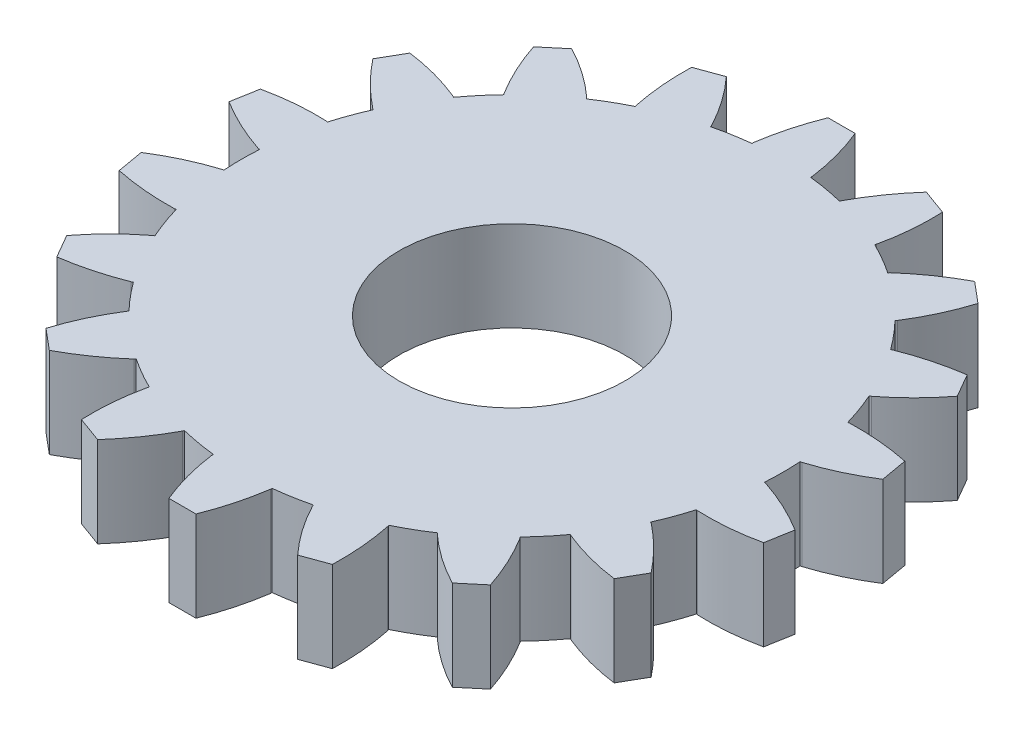
SolidWorks part; units mm, degrees
ref_plane "Front Plane" through (0, 0, 0) normal (0, 0, 1) x (1, 0, 0)
ref_plane "Top Plane" through (0, 0, 0) normal (0, 1, 0) x (1, 0, 0)
ref_plane "Right Plane" through (0, 0, 0) normal (1, 0, 0) x (0, 0, -1)
sketch "Sketch1" plane through (0, 0, 0) normal (0, 1, 0) x (1, 0, 0)
  circle A0 centre (0, 0) radius 6
  dimension "D1" = 12
extrude "Boss-Extrude1" add sketch "Sketch1" along normal blind 2
sketch "Sketch2" plane through (0, 2, 0) normal (0, 1, 0) x (1, 0, 0)
  circle A0 centre (0, 0) radius 1.25
  dimension "D1" = 2.5
extrude "Cut-Extrude1" cut sketch "Sketch2" against normal blind 4 and the other way blind 3
sketch "Sketch3" plane through (0, 2, 0) normal (0, 1, 0) x (1, 0, 0)
  circle A0 centre (0, 0) radius 2
  circle A1 centre (0, 0) radius 0.75
extrude "Boss-Extrude2" add sketch "Sketch3" along normal blind 0.2 and the other way blind 2.2
sketch "Sketch4" plane through (0, 2, 0) normal (0, 1, 0) x (1, 0, 0)
  line L3 (-0.3, 7.3) -> (0.3, 7.3)
  line L4 (-0.65, 6) -> (-0.65, 5.9647)
  line L5 (0.65, 6) -> (0.65, 5.9647)
  arc A1 (-0.3, 7.3) -> (-0.65, 6) centre (5.0734, 5.1562) ccw
  arc A2 (0.3, 7.3) -> (0.65, 6) centre (-4.488, 5.3138) cw
  arc A3 (0.65, 5.9647) -> (-0.65, 5.9647) centre (0, 0) ccw
  point P8 (-0.325, 6)
  point P11 (0, 7.3)
  dimension "D1" = 0.6
extrude "Boss-Extrude3" add sketch "Sketch4" against normal up to surface (2 mm away) up to face at (0, 0, 2)
ref_axis "Axis1" through (0, 2.32, 0) along (0, -1, 0)
pattern_circular "CirPattern1" count 18 over 360 about axis through (0, 2.32, 0) along (0, -1, 0) of "Boss-Extrude3"
sketch "Sketch5" plane through (0, 2, 0) normal (0, 1, 0) x (1, 0, 0)
  circle A0 centre (0, 0) radius 2.5
extrude "Cut-Extrude2" cut sketch "Sketch5" against normal blind 5 and the other way blind 3
